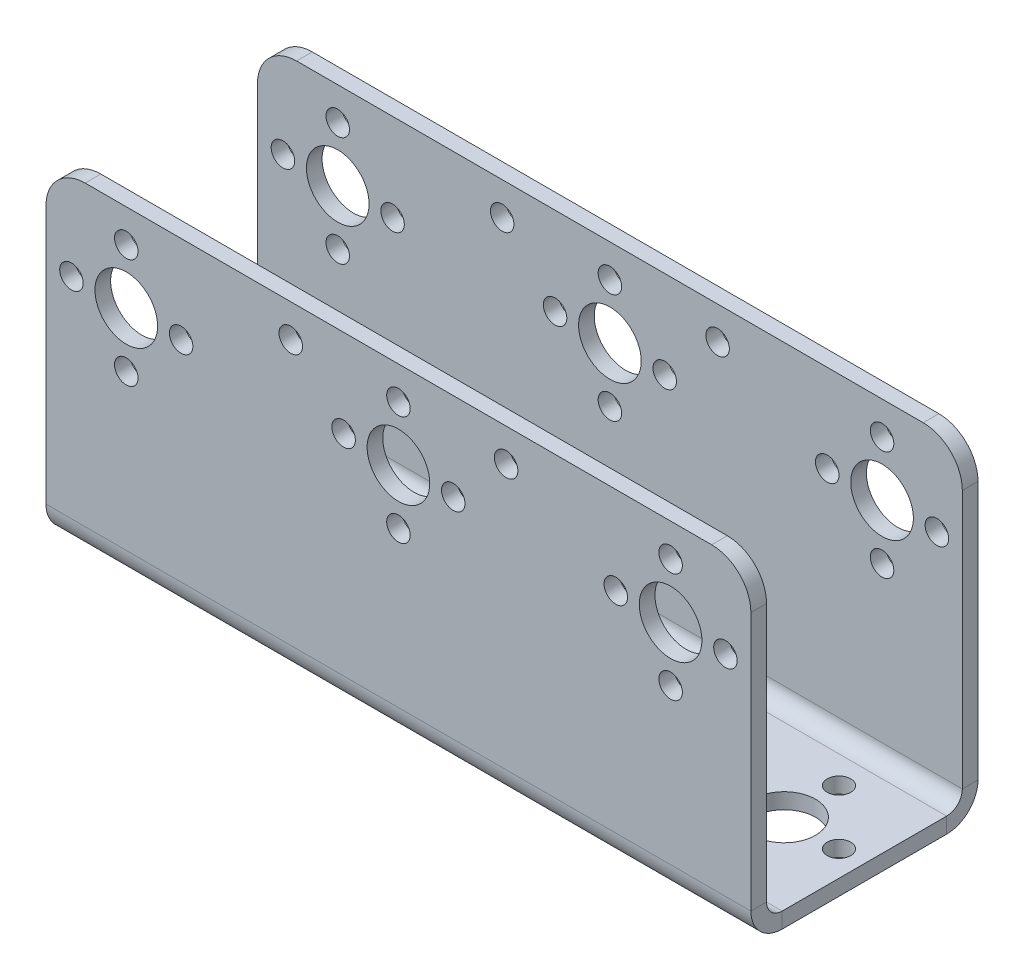
SolidWorks part; units mm, degrees
note: The reader was unsure of these and kept them because the rebuilt part matched: flange length of "Edge-Flange1".
material "6063-T1"
ref_plane "Plan de face" through (0, 0, 0) normal (0, 0, 1) x (1, 0, 0)
ref_plane "Plan de dessus" through (0, 0, 0) normal (0, 1, 0) x (1, 0, 0)
ref_plane "Plan de droite" through (0, 0, 0) normal (1, 0, 0) x (0, 0, -1)
ref_plane "Plan1" through (0, 0, 0) normal (0, 0, -1) x (-1, 0, 0)
sketch "Sketch1" plane through (0, 0, 0) normal (0, 0, 1) x (1, 0, 0)
  line L1 (-45, 0) -> (45, 0)
  line L2 (-45, 0) -> (-45, 37)
  line L3 (-40, 42) -> (40, 42)
  line L4 (45, 0) -> (45, 37)
  arc A0 (40, 42) -> (45, 37) centre (40, 37) cw
  arc A1 (-45, 37) -> (-40, 42) centre (-40, 37) cw
  point P7 (45, 42)
  point P10 (-45, 42)
  dimension "D3" = 5
  dimension "D1" = 90
  dimension "D2" = 42
base flange "Base-Flange1" sketch "Sketch1" thickness 2 reverse thickness direction no parameters "D1"=2
edge flange "Edge-Flange1" sketch "Sketch6" flange angle 90 flange length 12.5 flange position material inside bend radius 2 thickness 2 relief rectangular parameters "D6"=10
sketch "Sketch6" plane through (0, 0, -2) normal (0, -1, 0) x (-1, 0, 0)
  line L0 (45, 0) -> (-45, 0) construction
  line L1 (45, 0) -> (-45, 0)
  line L2 (-45, 0) -> (-45, 12.5)
  line L3 (-45, 12.5) -> (45, 12.5)
  line L4 (45, 12.5) -> (45, 0)
bend "EdgeBend1" bend radius 2 bend angle 90 parameters "D5"=1
mirror "Mirror1" about plane through (45, 0, -14.5) normal (0, 0, 1) of bodies 158
bend "MirrorBend1" bend radius 2 bend angle 90 parameters "D5"=2
sketch "Sketch11" plane through (0, 0, 0) normal (0, 0, 1) x (1, 0, 0)
  line L0 (-34.75, 30.8) -> (34.75, 30.8) construction
  line L1 (0, 30.8) -> (0, 0) construction
  line L2 (-45, 0) -> (45, 0) construction
  circle A0 centre (-34.75, 30.8) radius 4
  circle A1 centre (0, 30.8) radius 4
  circle A2 centre (34.75, 30.8) radius 4
  dimension "D1" = 8
  dimension "D2" = 30.8
  dimension "D3" = 34.75
extrude "Cut-Extrude1" cut sketch "Sketch11" against normal through all normal cut yes
hole_wizard "M3x0.5 Tapped Hole1" positions "Sketch13" profile "Sketch12" tap size "M3x0.5" standard "ANSI Metric" end condition through all
sketch "Sketch13" plane through (0, 0, 0) normal (0, 0, 1) x (1, 0, 0)
  line L4 (0, 37.8) -> (0, 23.8) construction
  line L6 (-7, 30.8) -> (7, 30.8) construction
  line L8 (34.75, 37.8) -> (34.75, 23.8) construction
  line L10 (41.75, 30.8) -> (27.75, 30.8) construction
  line L12 (-34.75, 37.8) -> (-34.75, 23.8) construction
  line L14 (-27.75, 30.8) -> (-41.75, 30.8) construction
  line L15 (13.75, 37.8) -> (-13.75, 37.8) construction
  circle A0 centre (0, 30.8) radius 7 construction
  circle A1 centre (-34.75, 30.8) radius 7 construction
  circle A2 centre (34.75, 30.8) radius 7 construction
  point P0 (-34.75, 37.8)
  point P2 (-34.75, 23.8)
  point P4 (-27.75, 30.8)
  point P6 (-41.75, 30.8)
  point P8 (0, 37.8)
  point P10 (0, 23.8)
  point P12 (-7, 30.8)
  point P14 (7, 30.8)
  point P45 (34.75, 37.8)
  point P46 (34.75, 23.8)
  point P47 (41.75, 30.8)
  point P48 (27.75, 30.8)
  point P74 (-13.75, 37.8)
  point P76 (13.75, 37.8)
  dimension "D1" = 14
  dimension "D2" = 13.75
sketch "Sketch12" plane through (-34.75, 37.8, 0) normal (1, 0, 0) x (0, -1, 0)
  line L0 (0, 0) -> (0, 29)
  line L1 (0, 29) -> (1.5, 29)
  line L2 (1.5, 29) -> (1.5, 0)
  line L5 (1.5, 0) -> (0, 0)
  line L11 (0, -6.35) -> (0, 107.95) construction
  dimension "Thread Major Dia." = 3
  dimension "Thru Tap Drill Depth" = 29
sketch "Sketch14" plane through (0, 2, 0) normal (0, 1, 0) x (1, 0, 0)
  line L0 (34.75, 14.5) -> (-34.75, 14.5) construction
  line L1 (0, 0) -> (0, 29) construction
  line L2 (40, 29) -> (-40, 29) construction
  circle A0 centre (-34.75, 14.5) radius 4
  circle A1 centre (0, 14.5) radius 4
  circle A2 centre (34.75, 14.5) radius 4
  dimension "D1" = 8
  dimension "D2" = 34.75
extrude "Cut-Extrude2" cut sketch "Sketch14" against normal through all normal cut yes
hole_wizard "M3x0.5 Tapped Hole2" positions "Sketch16" profile "Sketch15" tap size "M3x0.5" standard "ANSI Metric" end condition through all
sketch "Sketch16" plane through (0, 2, 0) normal (0, 1, 0) x (1, 0, 0)
  line L0 (-34.75, 21.5) -> (-34.75, 7.5) construction
  line L2 (-27.75, 14.5) -> (-41.75, 14.5) construction
  line L4 (0, 21.5) -> (0, 7.5) construction
  line L6 (-7, 14.5) -> (7, 14.5) construction
  line L8 (34.75, 21.5) -> (34.75, 7.5) construction
  line L10 (27.75, 14.5) -> (41.75, 14.5) construction
  circle A0 centre (0, 14.5) radius 7 construction
  circle A1 centre (34.75, 14.5) radius 7 construction
  circle A2 centre (-34.75, 14.5) radius 7 construction
  point P0 (-34.75, 21.5)
  point P2 (-34.75, 7.5)
  point P4 (-41.75, 14.5)
  point P6 (-27.75, 14.5)
  point P8 (0, 21.5)
  point P10 (0, 7.5)
  point P12 (-7, 14.5)
  point P14 (7, 14.5)
  point P16 (34.75, 21.5)
  point P18 (34.75, 7.5)
  point P20 (41.75, 14.5)
  point P22 (27.75, 14.5)
  dimension "D1" = 14
sketch "Sketch15" plane through (-34.75, 2, -21.5) normal (1, 0, 0) x (0, 0, 1)
  line L0 (0, 0) -> (0, 2)
  line L1 (0, 2) -> (1.5, 2)
  line L2 (1.5, 2) -> (1.5, 0)
  line L5 (1.5, 0) -> (0, 0)
  line L11 (0, -6.35) -> (0, 107.95) construction
  dimension "Thread Major Dia." = 3
  dimension "Thru Tap Drill Depth" = 2
sketch "Bend-Lines1" [suppressed] plane through (0, 0, 0) normal (0, 1, 0) x (1, 0, 0)
sketch "Bounding-Box1" [suppressed] plane through (0, 0, 0) normal (0, 1, 0) x (1, 0, 0)
sheet metal parameters "Sheet-Metal57" thickness 2 parameters "D1"=1
flat pattern "Flat-Pattern57" [suppressed]
sketch "Bend-Lines2" plane through (0, 0, 0) normal (0, 1, 0) x (1, 0, 0)
sketch3d "Bounding-Box2" [suppressed]
  line L0 (5, 5, 0) -> (-85, 5, 0) construction
  line L1 (5, -37, 0) -> (-85, -37, 0) construction
  line L2 (5, 5, 0) -> (5, -37, 0) construction
  line L3 (-85, 5, 0) -> (-85, -37, 0) construction
sheet metal parameters "Sheet-Metal58" thickness 2 parameters "D1"=1
flat pattern "Flat-Pattern57"
sketch "Bend-Lines2" plane through (0, 0, 0) normal (0, 0, 1) x (1, 0, 0)
  line L0 (-45, -0.1781) -> (45, -0.1781) construction
  line L1 (-45, -0.1781) -> (45, -0.1781) construction
sketch3d "Bounding-Box2" [suppressed]
  line L0 (-5, 5, 0) -> (85, 5, 0) construction
  line L1 (-5, -61.3562, 0) -> (85, -61.3562, 0) construction
  line L2 (-5, 5, 0) -> (-5, -61.3562, 0) construction
  line L3 (85, 5, 0) -> (85, -61.3562, 0) construction
bend of the flat pattern "Flatten-<EdgeBend1>1"
sheet metal parameters "Sheet-Metal59" thickness 2 parameters "D1"=1
flat pattern "Flat-Pattern59"
sketch "Bend-Lines3" plane through (0, 0, 0) normal (0, 0, 1) x (1, 0, 0)
  line L0 (-45, -23.5343) -> (45, -23.5343) construction
  line L1 (-45, -0.1781) -> (45, -0.1781) construction
  line L2 (-45, -23.5343) -> (45, -23.5343) construction
  line L3 (-45, -0.1781) -> (45, -0.1781) construction
sketch3d "Bounding-Box3" [suppressed]
  line L0 (85, -102.7124, 0) -> (85, 5, 0) construction
  line L1 (-5, -102.7124, 0) -> (-5, 5, 0) construction
  line L2 (85, -102.7124, 0) -> (-5, -102.7124, 0) construction
  line L3 (85, 5, 0) -> (-5, 5, 0) construction
bend of the flat pattern "Flatten-<EdgeBend1>2"
bend of the flat pattern "Flatten-<MirrorBend1>1"
sheet metal parameters "Sheet-Metal60" thickness 2 parameters "D1"=1
flat pattern "Flat-Pattern59"
sketch "Bend-Lines3" plane through (0, 0, 0) normal (0, 0, 1) x (1, 0, 0)
  line L0 (-45, -23.5343) -> (45, -23.5343) construction
  line L1 (-45, -0.1781) -> (45, -0.1781) construction
  line L2 (-45, -23.5343) -> (45, -23.5343) construction
  line L3 (-45, -0.1781) -> (45, -0.1781) construction
sketch3d "Bounding-Box3" [suppressed]
  line L0 (85, -102.7124, 0) -> (85, 5, 0) construction
  line L1 (-5, -102.7124, 0) -> (-5, 5, 0) construction
  line L2 (85, -102.7124, 0) -> (-5, -102.7124, 0) construction
  line L3 (85, 5, 0) -> (-5, 5, 0) construction
bend of the flat pattern "Flatten-<EdgeBend1>2"
bend of the flat pattern "Flatten-<MirrorBend1>1"
sheet metal parameters "Sheet-Metal61" thickness 2 parameters "D1"=1
flat pattern "Flat-Pattern59"
sketch "Bend-Lines3" plane through (0, 0, 0) normal (0, 0, 1) x (1, 0, 0)
  line L0 (-45, -23.5343) -> (45, -23.5343) construction
  line L1 (-45, -0.1781) -> (45, -0.1781) construction
  line L2 (-45, -23.5343) -> (45, -23.5343) construction
  line L3 (-45, -0.1781) -> (45, -0.1781) construction
sketch3d "Bounding-Box3" [suppressed]
  line L0 (85, -102.7124, 0) -> (85, 5, 0) construction
  line L1 (-5, -102.7124, 0) -> (-5, 5, 0) construction
  line L2 (85, -102.7124, 0) -> (-5, -102.7124, 0) construction
  line L3 (85, 5, 0) -> (-5, 5, 0) construction
bend of the flat pattern "Flatten-<EdgeBend1>2"
bend of the flat pattern "Flatten-<MirrorBend1>1"
sheet metal parameters "Sheet-Metal62" thickness 2 parameters "D1"=1
flat pattern "Flat-Pattern59"
sketch "Bend-Lines3" plane through (0, 0, 0) normal (0, 0, 1) x (1, 0, 0)
  line L0 (-45, -23.5343) -> (45, -23.5343) construction
  line L1 (-45, -0.1781) -> (45, -0.1781) construction
  line L2 (-45, -23.5343) -> (45, -23.5343) construction
  line L3 (-45, -0.1781) -> (45, -0.1781) construction
sketch3d "Bounding-Box3" [suppressed]
  line L0 (85, -102.7124, 0) -> (85, 5, 0) construction
  line L1 (-5, -102.7124, 0) -> (-5, 5, 0) construction
  line L2 (85, -102.7124, 0) -> (-5, -102.7124, 0) construction
  line L3 (85, 5, 0) -> (-5, 5, 0) construction
bend of the flat pattern "Flatten-<EdgeBend1>2"
bend of the flat pattern "Flatten-<MirrorBend1>1"
sheet metal parameters "Sheet-Metal63" thickness 2 parameters "D1"=1
flat pattern "Flat-Pattern59"
sketch "Bend-Lines3" plane through (0, 0, 0) normal (0, 0, 1) x (1, 0, 0)
  line L0 (-45, -24.0686) -> (45, -24.0686) construction
  line L1 (-45, 1.6438) -> (45, 1.6438) construction
  line L2 (-45, -24.0686) -> (45, -24.0686) construction
  line L3 (-45, 1.6438) -> (45, 1.6438) construction
sketch3d "Bounding-Box3" [suppressed]
  line L0 (85, -101.4248, 0) -> (85, 5, 0) construction
  line L1 (-5, -101.4248, 0) -> (-5, 5, 0) construction
  line L2 (85, -101.4248, 0) -> (-5, -101.4248, 0) construction
  line L3 (85, 5, 0) -> (-5, 5, 0) construction
bend of the flat pattern "Flatten-<EdgeBend1>2"
bend of the flat pattern "Flatten-<MirrorBend1>1"
equation "\"D7@Edge-Flange1\"=25/2"
